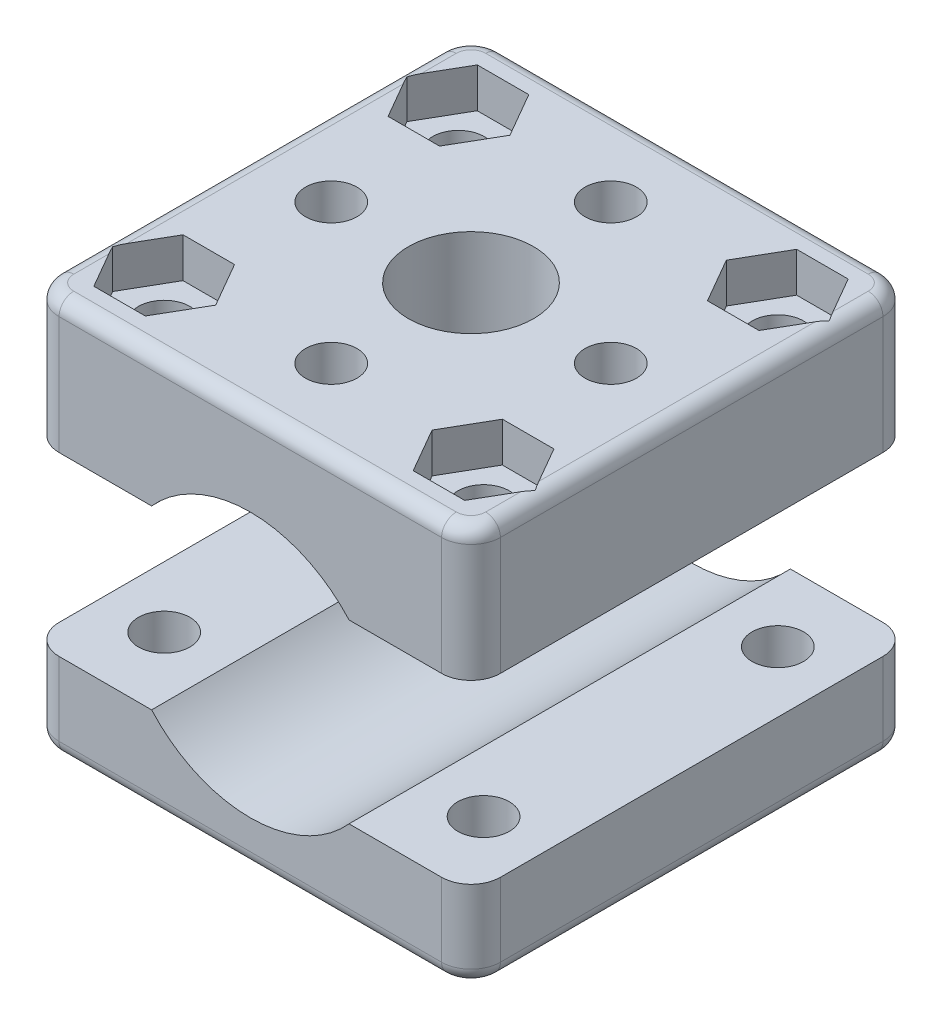
SolidWorks part; units mm, degrees
material "Manual Density from Real Component Supporto Motore VTOL"
ref_plane "Piano frontale" through (0, 0, 0) normal (0, 0, 1) x (1, 0, 0)
ref_plane "Piano superiore" through (0, 0, 0) normal (0, 1, 0) x (1, 0, 0)
ref_plane "Piano destro" through (0, 0, 0) normal (1, 0, 0) x (0, 0, -1)
sketch "Schizzo1" plane through (0, 0, 0) normal (0, 0, 1) x (1, 0, 0)
  line L0 (0, -55) -> (0, 55) construction
  line L1 (-15, 12) -> (15, 12) construction
  line L2 (-15, 12) -> (-15, 6)
  line L3 (-15, 6) -> (-6.7082, 6)
  line L4 (15, 12) -> (15, 6)
  line L5 (15, -6) -> (6.7082, -6)
  line L6 (15, -6) -> (15, -12)
  line L7 (15, -12) -> (-15, -12)
  line L8 (-15, -6) -> (-15, -12)
  line L9 (-15, 6) -> (-15, -6) construction
  line L10 (55, 0) -> (-55, 0) construction
  line L11 (-15, -9) -> (15, -9) construction
  line L12 (6.7082, 6) -> (15, 6)
  line L13 (-6.7082, -6) -> (-15, -6)
  line L14 (-15, 12) -> (-15, 15)
  line L15 (-15, 15) -> (15, 15)
  line L16 (15, 15) -> (15, 12)
  circle A0 centre (0, 0) radius 9 construction
  arc A1 (6.7082, 6) -> (-6.7082, 6) centre (0, 0) ccw
  arc A2 (6.7082, -6) -> (-6.7082, -6) centre (0, 0) cw
  point P11 (0, 12)
  point P14 (-15, 0)
  dimension "D1" = 18
  dimension "D2" = 30
  dimension "D3" = 6
  dimension "D4" = 3
  dimension "D5" = 3
extrude "Morsa" add sketch "Schizzo1" along normal blind 15 and the other way blind 15
sketch "LineaGuidaForiViti" plane through (0, 0, -15) normal (0, 0, -1) x (-1, 0, 0)
  line L0 (10.8541, 6) -> (10.8541, 15) construction
  line L1 (15, 6) -> (6.7082, 6) construction
  line L3 (10.8541, 10.5) -> (-15, 10.5) construction
  line L5 (-15, 15) -> (15, 15) construction
  line L6 (-15, 6) -> (-15, 15) construction
sketch "Schizzo2" plane through (0, 15, 0) normal (0, 1, 0) x (1, 0, 0)
  line L0 (-10.8541, 10) -> (-10.8541, 15) construction
  line L2 (0, -14.85) -> (0, 14.85) construction
  line L3 (-14.85, 0) -> (14.85, 0) construction
  circle A0 centre (-10.8541, 10) radius 1.75
  circle A1 centre (10.8541, 10) radius 1.75
  circle A2 centre (-10.8541, -10) radius 1.75
  circle A3 centre (10.8541, -10) radius 1.75
  dimension "D1" = 3.5
  dimension "D2" = 5
extrude "ForiVitiMorsa" cut sketch "Schizzo2" against normal through all
sketch "Schizzo4" plane through (0, 15, 0) normal (0, 1, 0) x (1, 0, 0)
  line L0 (0, -14.85) -> (0, 14.85) construction
  line L1 (-14.85, 0) -> (14.85, 0) construction
  circle A0 centre (0, -9.5) radius 1.75
  circle A1 centre (9.5, 0) radius 1.75
  circle A2 centre (0, 0) radius 9.5 construction
  circle A3 centre (-9.5, 0) radius 1.75
  circle A4 centre (0, 9.5) radius 1.75
  point P11 (0, 0)
  dimension "D1" = 3.5
  dimension "D2" = 19
extrude "ForiVitiMotore" cut sketch "Schizzo4" against normal up to surface (9 mm away) up to face at (10.8541, 6, -11.75)
sketch "Schizzo5" plane through (0, 15, 0) normal (0, 1, 0) x (1, 0, 0)
  line L1 (-9.1041, -13.0311) -> (-7.3541, -10)
  line L2 (-7.3541, -10) -> (-9.1041, -6.9689)
  line L3 (-9.1041, -6.9689) -> (-12.6041, -6.9689)
  line L4 (-12.6041, -6.9689) -> (-14.3541, -10)
  line L5 (-14.3541, -10) -> (-12.6041, -13.0311)
  line L6 (-12.6041, -13.0311) -> (-9.1041, -13.0311)
  line L13 (9.1041, -6.9689) -> (7.3541, -10)
  line L14 (7.3541, -10) -> (9.1041, -13.0311)
  line L15 (9.1041, -13.0311) -> (12.6041, -13.0311)
  line L16 (12.6041, -13.0311) -> (14.3541, -10)
  line L17 (14.3541, -10) -> (12.6041, -6.9689)
  line L18 (12.6041, -6.9689) -> (9.1041, -6.9689)
  line L32 (9.1041, 6.9689) -> (12.6041, 6.9689)
  line L33 (12.6041, 6.9689) -> (14.3541, 10)
  line L34 (14.3541, 10) -> (12.6041, 13.0311)
  line L35 (12.6041, 13.0311) -> (9.1041, 13.0311)
  line L36 (9.1041, 13.0311) -> (7.3541, 10)
  line L37 (7.3541, 10) -> (9.1041, 6.9689)
  line L44 (-14.3541, 10) -> (-12.6041, 6.9689)
  line L45 (-12.6041, 6.9689) -> (-9.1041, 6.9689)
  line L46 (-9.1041, 6.9689) -> (-7.3541, 10)
  line L47 (-7.3541, 10) -> (-9.1041, 13.0311)
  line L48 (-9.1041, 13.0311) -> (-12.6041, 13.0311)
  line L49 (-12.6041, 13.0311) -> (-14.3541, 10)
  circle A0 centre (-10.8541, -10) radius 3.0311 construction
  circle A1 centre (9.5, 0) radius 1.75
  circle A2 centre (10.8541, -10) radius 3.0311 construction
  circle A3 centre (0, -9.5) radius 3 construction
  circle A4 centre (-9.5, 0) radius 1.75
  circle A5 centre (0, 9.5) radius 3 construction
  circle A6 centre (10.8541, 10) radius 3.0311 construction
  circle A8 centre (-10.8541, 10) radius 3.0311 construction
  circle A9 centre (0, 9.5) radius 1.75 construction
  dimension "D2" = 3.5
  dimension "D3" = 6
  dimension "D1" = 3.5
extrude "ForoEsagonalePiastre" cut sketch "Schizzo5" against normal blind 2.7
ref_plane "PianoVite" through (0, 0, 10) normal (0, 0, 1) x (1, 0, 0)
sketch "Schizzo6" plane through (0, -12, 0) normal (0, -1, 0) x (1, 0, 0)
  circle A0 centre (-10.8541, 10) radius 3.25
  circle A1 centre (10.8541, 10) radius 3.25
  circle A2 centre (-10.8541, -10) radius 3.25
  circle A3 centre (10.8541, -10) radius 3.25
  dimension "D1" = 6.5
extrude "SvasaturaVitiInferiori" cut sketch "Schizzo6" against normal blind 3
sketch "Schizzo7" plane through (0, 6, 0) normal (0, -1, 0) x (1, 0, 0)
  circle A0 centre (9.5, 0) radius 1.75 construction
  circle A1 centre (9.5, 0) radius 3.25
  circle A2 centre (-9.5, 0) radius 3.25
  circle A3 centre (-9.5, 0) radius 1.75 construction
  dimension "D1" = 6.5
extrude "SvasaturaVitiMotoriAlte" cut sketch "Schizzo7" against normal blind 3
ref_plane "PianoTangenteSuperiore" through (0, 9, 0) normal (0, 1, 0) x (1, 0, 0)
sketch "Schizzo8" plane through (0, 9, 0) normal (0, 1, 0) x (1, 0, 0)
  circle A0 centre (0, 9.5) radius 3.25
  circle A1 centre (0, -9.5) radius 3.25
  circle A2 centre (-9.5, 0) radius 3.25 construction
extrude "SvasaturaVitiMotoriBasse" cut sketch "Schizzo8" along normal blind 3 and the other way blind 1
sketch "Schizzo9" plane through (0, 15, 0) normal (0, 1, 0) x (1, 0, 0)
  circle A0 centre (0, 0) radius 4.25
  dimension "D1" = 8.5
extrude "ForoMotore" cut sketch "Schizzo9" against normal up to surface (6 mm away) up to face at (0.52, 8.985, -12.7081)
fillet "RaccordoVerticaleUp" radius 2 4 edges at (-15, 10.5, 15) (-15, 10.5, -15) (15, 10.5, 15) (15, 10.5, -15)
fillet "RaccordoVerticaleDown" radius 2 4 edges at (15, -9, -15) (-15, -9, -15) (15, -9, 15) (-15, -9, 15)
fillet "RaccordoOrizzontaleUp" radius 1 8 edges at (-14.4142, 15, 14.4142) (-15, 15, 0) (-14.4142, 15, -14.4142) (0, 15, -15) (14.4142, 15, -14.4142) (0, 15, 15) (14.4142, 15, 14.4142) (15, 15, 0)
fillet "RaccordoOrizzontaleDown" radius 1 8 edges at (0, -12, -15) (-14.4142, -12, -14.4142) (-15, -12, 0) (-14.4142, -12, 14.4142) (14.4142, -12, -14.4142) (15, -12, 0) (14.4142, -12, 14.4142) (0, -12, 15)
